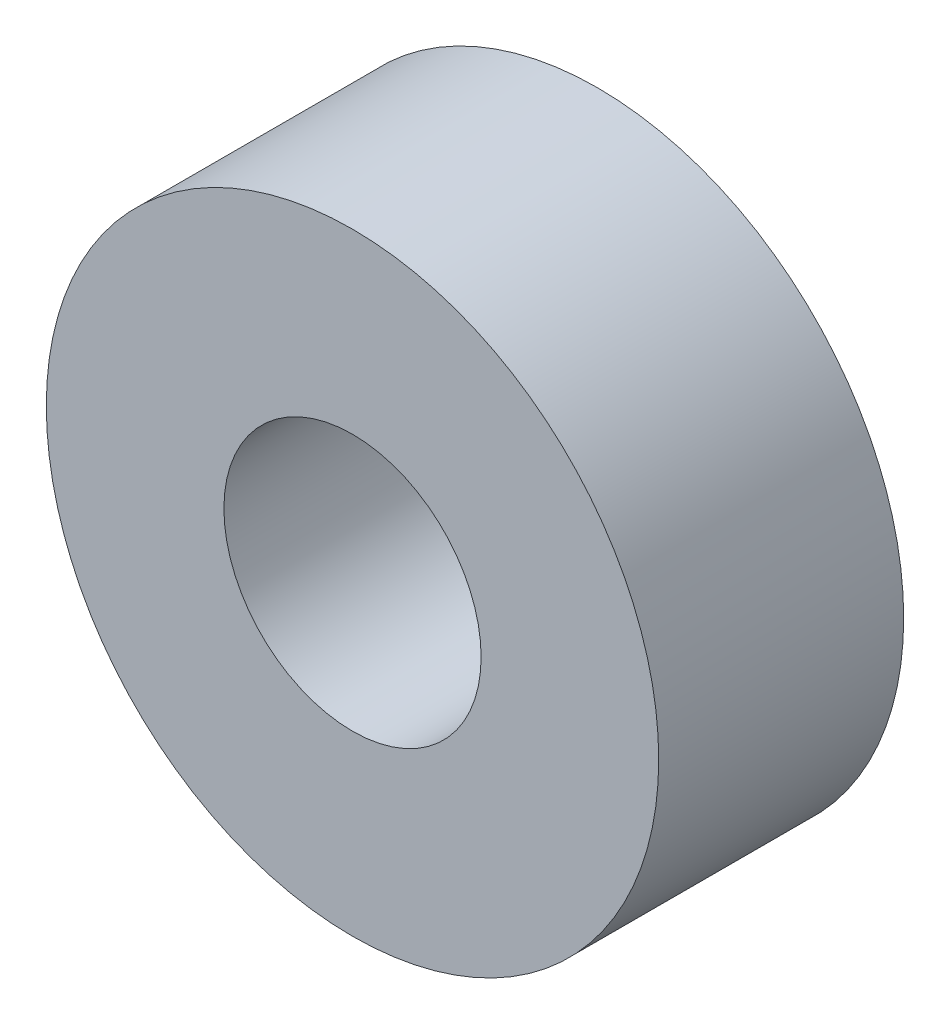
SolidWorks part; units mm, degrees
ref_plane "Front Plane" through (0, 0, 0) normal (0, 0, 1) x (1, 0, 0)
ref_plane "Top Plane" through (0, 0, 0) normal (0, 1, 0) x (1, 0, 0)
ref_plane "Right Plane" through (0, 0, 0) normal (1, 0, 0) x (0, 0, -1)
sketch "Sketch1" plane through (0, 0, 0) normal (0, 0, 1) x (1, 0, 0)
  circle A0 centre (0, 0) radius 2.1
  circle A1 centre (0, 0) radius 5
  dimension "D1" = 4.2
  dimension "D2" = 10
extrude "Boss-Extrude1" add sketch "Sketch1" along normal blind 4
